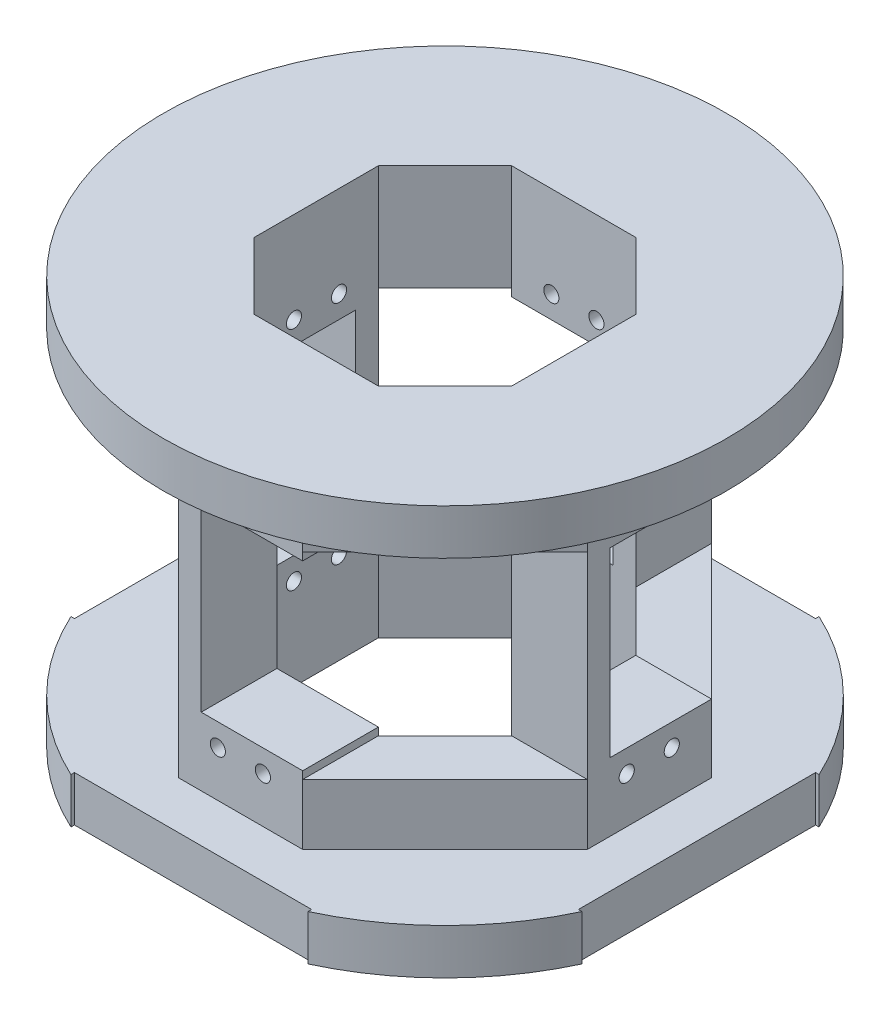
SolidWorks part; units mm, degrees
ref_plane "Front Plane" through (0, 0, 0) normal (0, 0, 1) x (1, 0, 0)
ref_plane "Top Plane" through (0, 0, 0) normal (0, 1, 0) x (1, 0, 0)
ref_plane "Right Plane" through (0, 0, 0) normal (1, 0, 0) x (0, 0, -1)
sketch "Sketch1" plane through (0, 0, 0) normal (0, 1, 0) x (1, 0, 0)
  line L0 (0, 33) -> (0, -33) construction
  line L1 (-33, 0) -> (33, 0) construction
  circle A0 centre (0, 0) radius 38.1 construction
  point P6 (0, 0)
  point P9 (0, 33)
  point P10 (0, 0)
  point P12 (0, -33)
  dimension "D1" = 76.2
  dimension "D2" = 66
  dimension "D3" = 66
sketch "Sketch2" plane through (0, 0, 0) normal (1, 0, 0) x (0, 0, -1)
  line L0 (-33, 0) -> (-27, 0) construction
  line L1 (38.1, 0) -> (-38.1, 0) construction
  line L2 (-27, 21) -> (-27, -21)
  line L3 (-27, 21) -> (-17, 21)
  line L5 (-27, -21) -> (-17, -21)
  line L6 (-17, 21) -> (-17, -21)
  point P8 (-27, 0)
  point P12 (0, 0)
  dimension "D1" = 6
  dimension "D2" = 42
  dimension "D3" = 10
extrude "Boss-Extrude1" add sketch "Sketch2" along normal blind 8.2 and the other way blind 8.2 contours L2 L5 L6 L3
sketch "Sketch4" plane through (0, 0, 27) normal (0, 0, 1) x (1, 0, 0)
  line L1 (-8.2, 21) -> (-8.2, -21) construction
  line L2 (-5.2, 12) -> (8.2, 12)
  line L6 (-5.2, 12) -> (-5.2, -12)
  line L11 (-5.2, -12) -> (8.2, -12)
  line L12 (8.2, 12) -> (8.2, -12)
  line L14 (-8.2, -21) -> (8.2, -21) construction
  line L15 (-8.2, 21) -> (8.2, 21) construction
  circle A0 centre (-3, 14.95) radius 1
  circle A1 centre (2.95, 14.95) radius 1
  circle A2 centre (-3, -14.95) radius 1
  circle A3 centre (2.95, -14.95) radius 1
  point P3 (-5.2, 0)
  dimension "D6" = 2
  dimension "D7" = 5.2
  dimension "D8" = 5.95
  dimension "D9" = 2.95
  dimension "D10" = 2.95
  dimension "D11" = 2
  dimension "D12" = 2
  dimension "D13" = 2.95
  dimension "D14" = 2.95
  dimension "D15" = 5.95
  dimension "D1" = 3
  dimension "D2" = 24
  dimension "D3" = 9
  dimension "D4" = 9
  dimension "D5" = 13.4
  dimension "D16" = 5.2
extrude "Cut-Extrude1" cut sketch "Sketch4" against normal through all both and the other way through all
sketch "Sketch19" plane through (0, 0, 0) normal (1, 0, 0) x (0, 0, -1)
  line L0 (0, 12.6902) -> (0, -12.6902)
  point P4 (0, 0)
pattern_circular "CirPattern1" count 4 over 360 about axis through (0, 12.6902, 0) along (0, -1, 0) reverse direction yes of bodies 114
sketch "Sketch20" plane through (0, 21, 0) normal (0, 1, 0) x (1, 0, 0)
  line L0 (-17, 8.2) -> (-8.2, 17)
  line L1 (-8.2, 17) -> (-8.2, 27)
  line L2 (-8.2, 27) -> (-27, 8.2)
  line L3 (-27, 8.2) -> (-17, 8.2)
  line L4 (-17, -8.2) -> (-8.2, -17)
  line L5 (-17, 8.2) -> (-17, -8.2) construction
  line L6 (-8.2, -17) -> (-8.2, -27)
  line L7 (-8.2, -27) -> (-27, -8.2)
  line L8 (-27, -8.2) -> (-17, -8.2)
  line L9 (8.2, -17) -> (17, -8.2)
  line L10 (17, -8.2) -> (27, -8.2)
  line L11 (27, -8.2) -> (27, 8.2) construction
  line L12 (27, -8.2) -> (17, -8.2) construction
  line L13 (27, -8.2) -> (8.2, -27)
  line L14 (8.2, -27) -> (8.2, -17)
  line L15 (8.2, 17) -> (17, 8.2)
  line L16 (27, 8.2) -> (17, 8.2) construction
  line L17 (17, -8.2) -> (17, 8.2) construction
  line L18 (17, 8.2) -> (27, 8.2)
  line L19 (27, 8.2) -> (8.2, 27)
  line L20 (8.2, 27) -> (8.2, 17) construction
  line L21 (8.2, 27) -> (8.2, 17)
  dimension "D1" = 12.4451
  dimension "D2" = 12.4451
  dimension "D3" = 12.4451
  dimension "D4" = 12.4451
extrude "Boss-Extrude2" add sketch "Sketch20" against normal blind 8
sketch "Sketch21" plane through (0, -21, 0) normal (0, -1, 0) x (1, 0, 0)
  line L0 (-17, 8.2) -> (-8.2, 17)
  line L1 (-17, -8.2) -> (-17, 8.2) construction
  line L2 (-8.2, 27) -> (-8.2, 17) construction
  line L3 (-8.2, 27) -> (-8.2, 17) construction
  line L7 (17, -8.2) -> (8.2, -17)
  line L9 (-8.2, -17) -> (-17, -8.2)
  line L11 (-8.2, 17) -> (-8.2, 27)
  line L12 (-27, 8.2) -> (-8.2, 27) construction
  line L13 (-8.2, 27) -> (-27, 8.2)
  line L14 (-27, 8.2) -> (-17, 8.2)
  line L15 (8.2, 17) -> (17, 8.2)
  line L17 (17, 8.2) -> (27, 8.2)
  line L18 (27, 8.2) -> (27, -8.2) construction
  line L19 (27, 8.2) -> (17, 8.2) construction
  line L20 (27, 8.2) -> (8.2, 27)
  line L21 (8.2, 27) -> (8.2, 17)
  line L22 (8.2, -17) -> (8.2, -27)
  line L23 (8.2, -27) -> (27, -8.2)
  line L24 (27, -8.2) -> (17, -8.2)
  line L25 (-27, -8.2) -> (-17, -8.2)
  line L26 (-27, -8.2) -> (-8.2, -27)
  line L27 (-8.2, -27) -> (-8.2, -17)
extrude "Boss-Extrude3" add sketch "Sketch21" against normal blind 8
sketch "Sketch22" plane through (0, -21, 0) normal (0, -1, 0) x (1, 0, 0)
  line L0 (-33.7417, 15.6632) -> (-33.2744, 15.6632)
  line L3 (-15.6632, -33.2744) -> (15.6632, -33.2744)
  line L4 (15.6632, -33.7417) -> (15.6632, -33.2744)
  line L8 (-33.7417, -15.6632) -> (-33.2744, -15.6632)
  line L9 (-33.2744, 15.6632) -> (-33.2744, -15.6632)
  line L10 (15.6632, 33.7417) -> (15.6632, 33.2744)
  line L12 (-15.6632, 33.7417) -> (-15.6632, 33.2744)
  line L13 (15.6632, 33.2744) -> (-15.6632, 33.2744)
  line L14 (33.7417, -15.6632) -> (33.2744, -15.6632)
  line L16 (33.7417, 15.6632) -> (33.2744, 15.6632)
  line L17 (33.2744, -15.6632) -> (33.2744, 15.6632)
  line L18 (-15.6632, -33.7417) -> (-15.6632, -33.2744)
  arc A0 (15.6632, -33.7417) -> (33.7417, -15.6632) centre (0, 0) ccw
  arc A1 (33.7417, 15.6632) -> (15.6632, 33.7417) centre (0, 0) ccw
  arc A2 (-33.7417, -15.6632) -> (-15.6632, -33.7417) centre (0, 0) ccw
  arc A3 (-15.6632, 33.7417) -> (-33.7417, 15.6632) centre (0, 0) ccw
  point P22 (0, 0)
  line M2 (-17, 8.2) -> (-8.2, 17)
  line M3 (-8.2, 17) -> (8.2, 17)
  line M4 (8.2, 17) -> (17, 8.2)
  line M5 (17, 8.2) -> (17, -8.2)
  line M6 (17, -8.2) -> (8.2, -17)
  line M7 (8.2, -17) -> (-8.2, -17)
  line M8 (-8.2, -17) -> (-17, -8.2)
  line M9 (-17, -8.2) -> (-17, 8.2)
  line M10 (8.2, 27) -> (-8.2, 27)
  line M11 (-8.2, 27) -> (-27, 8.2)
  line M12 (-27, 8.2) -> (-27, -8.2)
  line M13 (-27, -8.2) -> (-8.2, -27)
  line M14 (-8.2, -27) -> (8.2, -27)
  line M15 (8.2, -27) -> (27, -8.2)
  line M16 (27, -8.2) -> (27, 8.2)
  line M17 (27, 8.2) -> (8.2, 27)
  dimension "D1" = 74.4
  dimension "D4" = 4
extrude "Boss-Extrude4" add sketch "Sketch22" along normal blind 6 contours M17 M10 M11 M12 M13 M14 M15 M16 M9 M2 M3 M4 M5 M6 M7 M8 | A0 M10 M17 M16 M15 M14 M13 M12 M11 region at (-25.6295, -21, 25.6295) region at (17.06, -21, 17.06)
sketch "Sketch23" plane through (0, 21, 0) normal (0, 1, 0) x (1, 0, 0)
  circle A0 centre (0, 0) radius 37.2
  line M2 (-8.2, 17) -> (8.2, 17)
  line M3 (8.2, 17) -> (17, 8.2)
  line M4 (17, 8.2) -> (17, -8.2)
  line M5 (17, -8.2) -> (8.2, -17)
  line M6 (8.2, -17) -> (-8.2, -17)
  line M7 (-8.2, -17) -> (-17, -8.2)
  line M8 (-17, -8.2) -> (-17, 8.2)
  line M9 (-17, 8.2) -> (-8.2, 17)
  dimension "D1" = 74.4
extrude "Boss-Extrude5" add sketch "Sketch23" along normal blind 6 contours M2 M9 M8 M7 M6 M5 M4 M3 | A0 region at (0, 21, 0)
